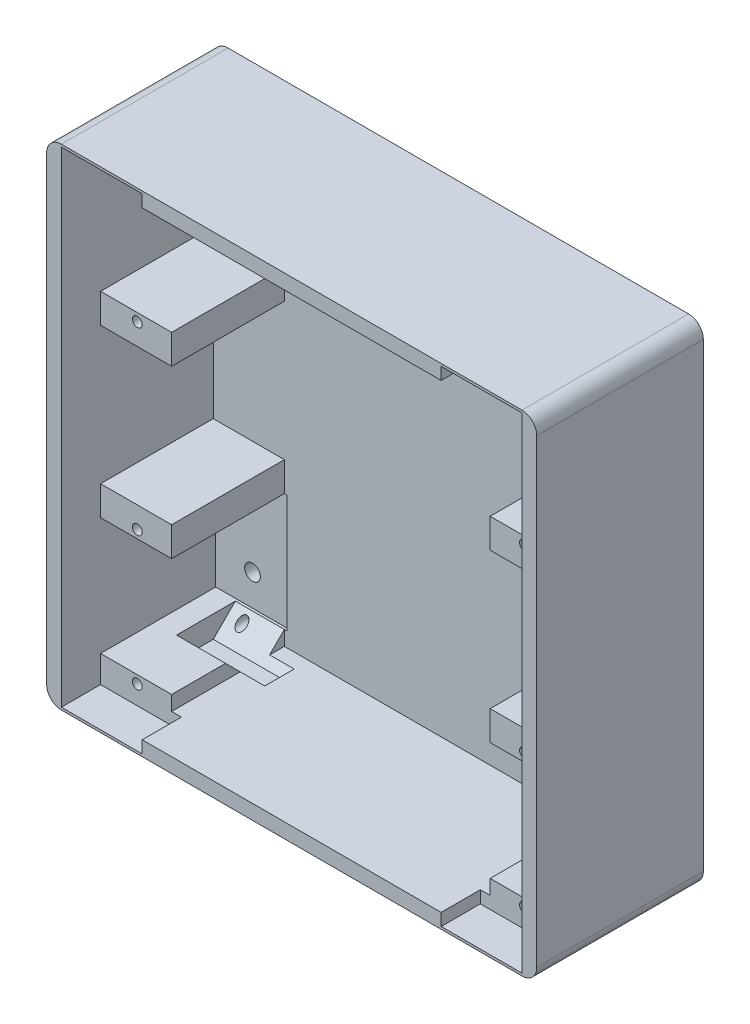
SolidWorks part; units mm, degrees
ref_plane "Plano frontal" through (0, 0, 0) normal (0, 0, 1) x (1, 0, 0)
ref_plane "Plano superior" through (0, 0, 0) normal (0, 1, 0) x (1, 0, 0)
ref_plane "Plano direito" through (0, 0, 0) normal (1, 0, 0) x (0, 0, -1)
sketch "Esboço1" plane through (0, 0, 0) normal (0, 0, 1) x (1, 0, 0)
  line L0 (39.5, 45.65) -> (39.5, 18.35) construction
  line L1 (-50, 50) -> (50, 50)
  line L2 (-50, 50) -> (-50, -50)
  line L3 (-50, -50) -> (50, -50)
  line L4 (50, 50) -> (50, -50)
  line L5 (-50, 50) -> (50, -50) construction
  line L6 (-50, -50) -> (50, 50) construction
  line L7 (32, 44) -> (47, 44)
  line L8 (32, 44) -> (32, 20)
  line L9 (32, 20) -> (47, 20)
  line L10 (47, 44) -> (47, 20)
  line L11 (32, 44) -> (47, 20) construction
  line L12 (32, 20) -> (47, 44) construction
  line L13 (-11.651, 0) -> (14.1427, 0) construction
  line L14 (0, 12.3596) -> (0, -15.2082) construction
  line L15 (32, -20) -> (47, -44) construction
  line L16 (32, -44) -> (47, -20) construction
  line L17 (39.5, -45.65) -> (39.5, -18.35) construction
  line L18 (47, -44) -> (47, -20)
  line L19 (32, -20) -> (47, -20)
  line L20 (32, -44) -> (32, -20)
  line L21 (32, -44) -> (47, -44)
  line L22 (-39.5, -45.65) -> (-39.5, -18.35) construction
  line L23 (-32, -44) -> (-47, -20) construction
  line L24 (-32, -20) -> (-47, -44) construction
  line L25 (-32, 20) -> (-47, 44) construction
  line L26 (-32, 44) -> (-47, 20) construction
  line L27 (-39.5, 45.65) -> (-39.5, 18.35) construction
  line L28 (-32, -44) -> (-47, -44)
  line L29 (-32, -44) -> (-32, -20)
  line L30 (-32, -20) -> (-47, -20)
  line L31 (-47, -44) -> (-47, -20)
  line L32 (-47, 44) -> (-47, 20)
  line L33 (-32, 20) -> (-47, 20)
  line L34 (-32, 44) -> (-32, 20)
  line L35 (-32, 44) -> (-47, 44)
  line L37 (5.2789, -11.1404) -> (5.2789, 35.8596) construction
  line L38 (5.2789, -11.1404) -> (40.2789, -11.1404) construction
  line L39 (40.2789, -11.1404) -> (40.2789, 35.8596) construction
  line L40 (5.2789, 35.8596) -> (40.2789, 35.8596) construction
  line L41 (5.2789, -11.1404) -> (40.2789, 35.8596) construction
  line L42 (40.2789, -11.1404) -> (5.2789, 35.8596) construction
  line L43 (-31.1, -20.1621) -> (31.1, -20.1621) construction
  line L44 (-31.1, -20.1621) -> (-31.1, -42.4621) construction
  line L45 (-31.1, -42.4621) -> (31.1, -42.4621) construction
  line L46 (31.1, -20.1621) -> (31.1, -42.4621) construction
  line L47 (-31.1, -20.1621) -> (31.1, -42.4621) construction
  line L48 (-31.1, -42.4621) -> (31.1, -20.1621) construction
  circle A0 centre (39.5, 18.35) radius 1
  circle A1 centre (39.5, 45.65) radius 1
  circle A2 centre (39.5, 36.5) radius 7.5 construction
  circle A3 centre (39.5, -36.5) radius 7.5 construction
  circle A4 centre (39.5, -45.65) radius 1
  circle A5 centre (39.5, -18.35) radius 1
  circle A6 centre (-39.5, -36.5) radius 7.5 construction
  circle A7 centre (-39.5, 36.5) radius 7.5 construction
  circle A8 centre (-39.5, -18.35) radius 1
  circle A9 centre (-39.5, -45.65) radius 1
  circle A10 centre (-39.5, 45.65) radius 1
  circle A11 centre (-39.5, 18.35) radius 1
  point P0 (0, 0)
  point P6 (39.5, 32)
  point P18 (39.5, 32)
  point P33 (39.5, -32)
  point P54 (-39.5, -32)
  point P55 (-39.5, 32)
  point P56 (22.7789, 12.3596)
  point P61 (0, -31.3121)
  dimension "D4" = 2
  dimension "D1" = 24
  dimension "D2" = 15
  dimension "D3" = 3
  dimension "D5" = 27.3
  dimension "D6" = 6
  dimension "D7" = 47
  dimension "D8" = 35
  dimension "D9" = 62.2
  dimension "D10" = 22.3
  dimension "D11" = 100
  dimension "D12" = 100
  dimension "D13" = 13.5
  dimension "D14" = 10.5
extrude "Ressalto-extrusão1" add sketch "Esboço1" along normal blind 26
sketch "Esboço3" plane through (0, 0, 26) normal (0, 0, 1) x (1, 0, 0)
  line L0 (-32, 32) -> (-32.5, 32) construction
  line L1 (-32.5, 47) -> (32.5, 47)
  line L2 (-32.5, 47) -> (-32.5, 14)
  line L3 (-32.5, -47) -> (32.5, -47)
  line L4 (32.5, 47) -> (32.5, 14)
  line L5 (-32, 20) -> (-32, 44) construction
  line L6 (-32.5, -14) -> (-47, -14)
  line L7 (32, 44) -> (32, 20) construction
  line L9 (0, 50) -> (0, 47) construction
  line L10 (47, -14) -> (32.5, -14)
  line L11 (47, -14) -> (47, 14)
  line L12 (50, 50) -> (-50, 50) construction
  line L13 (0, -50) -> (0, -47) construction
  line L14 (-50, -50) -> (50, -50) construction
  line L15 (47, 14) -> (32.5, 14)
  line L16 (-47, -14) -> (-47, 14)
  line L17 (47, -14) -> (-47, 14) construction
  line L18 (47, 14) -> (-47, -14) construction
  line L19 (32.5, -14) -> (32.5, -47)
  line L20 (-32.5, -14) -> (-32.5, -47)
  line L21 (-32.5, 14) -> (-47, 14)
  line L22 (-50, 50) -> (-50, -50) construction
  line L23 (-32, -20) -> (-47, -20) construction
  point P8 (0, 0)
  dimension "D1" = 0.5
  dimension "D2" = 3
  dimension "D3" = 3
  dimension "D4" = 6
  dimension "D5" = 0.5
extrude "Corte-extrusão1" cut sketch "Esboço3" against normal offset from surface (23 mm away) 3 up to face at (-39.5, -32, 0)
sketch "Esboço4" plane through (0, 0, 0) normal (0, 0, -1) x (-1, 0, 0)
  line L0 (-47, -44) -> (-47, -20) construction
  line L1 (50, 50) -> (-50, 50)
  line L2 (50, 50) -> (50, -50)
  line L3 (50, -50) -> (-50, -50)
  line L4 (-50, 50) -> (-50, -50)
  line L5 (50, 50) -> (-50, -50) construction
  line L6 (50, -50) -> (-50, 50) construction
  line L7 (-32, -44) -> (-47, -44) construction
  line L9 (-14.847, 0) -> (0, 0) construction
  line L10 (0, -11.1268) -> (0, 0) construction
  circle A0 centre (-39.5, -37.65) radius 1.6
  circle A1 centre (-39.5, 37.65) radius 1.6
  circle A2 centre (39.5, 37.65) radius 1.6
  circle A3 centre (39.5, -37.65) radius 1.6
  point P0 (0, 0)
  point P11 (-47, -32)
  point P15 (-39.5, -44)
  dimension "D2" = 3.2
  dimension "D1" = 5.65
extrude "Ressalto-extrusão2" add sketch "Esboço4" against normal blind 2.5
sketch "Esboço5" plane through (0, 0, 26) normal (0, 0, 1) x (1, 0, 0)
  line L0 (32.5, 47) -> (-32.5, 47) construction
  line L1 (-50, -50) -> (50, -50)
  line L2 (-50, -50) -> (-50, 50)
  line L3 (-50, 50) -> (50, 50)
  line L4 (50, -50) -> (50, 50)
  line L5 (-50, -50) -> (50, 50) construction
  line L6 (-50, 50) -> (50, -50) construction
  line L7 (30.5, -47) -> (-30.5, -47)
  line L8 (47, -49.5) -> (47, 49.5)
  line L9 (30.5, 47) -> (-30.5, 47)
  line L10 (-47, -49.5) -> (-47, 49.5)
  line L13 (-47, 14) -> (-47, -14) construction
  line L14 (-47, 49.5) -> (-30.5, 49.5)
  line L15 (-30.5, 49.5) -> (-30.5, 47)
  line L16 (-32.5, 44) -> (-47, 44) construction
  line L17 (-32.5, 44) -> (-32.5, 47) construction
  line L18 (0, 28.5252) -> (0, 0) construction
  line L19 (0, 0) -> (24.9408, 0) construction
  line L20 (30.5, 49.5) -> (30.5, 47)
  line L21 (47, 49.5) -> (30.5, 49.5)
  line L22 (30.5, -49.5) -> (30.5, -47)
  line L23 (47, -49.5) -> (30.5, -49.5)
  line L24 (-30.5, -49.5) -> (-30.5, -47)
  line L25 (-47, -49.5) -> (-30.5, -49.5)
  point P0 (0, 0)
  point P7 (0, 0)
  dimension "D1" = 5.5
  dimension "D2" = 2
extrude "Ressalto-extrusão3" add sketch "Esboço5" along normal blind 8
fillet "Filete1" radius 3 4 edges at (-50, -50, 17) (50, -50, 17) (50, 50, 17) (-50, 50, 17)
sketch "Esboço6" plane through (-32.5, 0, 0) normal (1, 0, 0) x (0, 0, -1)
  line L0 (-15, 44) -> (-10.5, 48.5)
  line L1 (-26, 44) -> (-3, 44) construction
  line L3 (-10.5, 48.5) -> (-7.5, 48.5)
  line L4 (-7.5, 48.5) -> (-3, 44)
  line L5 (-9, 48.5) -> (-9, 44) construction
  line L6 (-15, 44) -> (-3, 44)
  line L7 (-3, 44) -> (-3, 47) construction
  point P8 (-9, 44)
  point P9 (0, 0)
  dimension "D1" = 45
  dimension "D2" = 3
  dimension "D3" = 4.5
extrude "Corte-extrusão2" cut sketch "Esboço6" against normal blind 10 and the other way blind 5
mirror "Espelhar1" about plane through (0, 0, 0) normal (1, 0, 0) of "Corte-extrusão2"
mirror "Espelhar2" about plane through (0, 0, 0) normal (0, 1, 0) of "Corte-extrusão2", "Espelhar1"
equation "\"D3@Esboço3\"=\"D2@Esboço3\""
